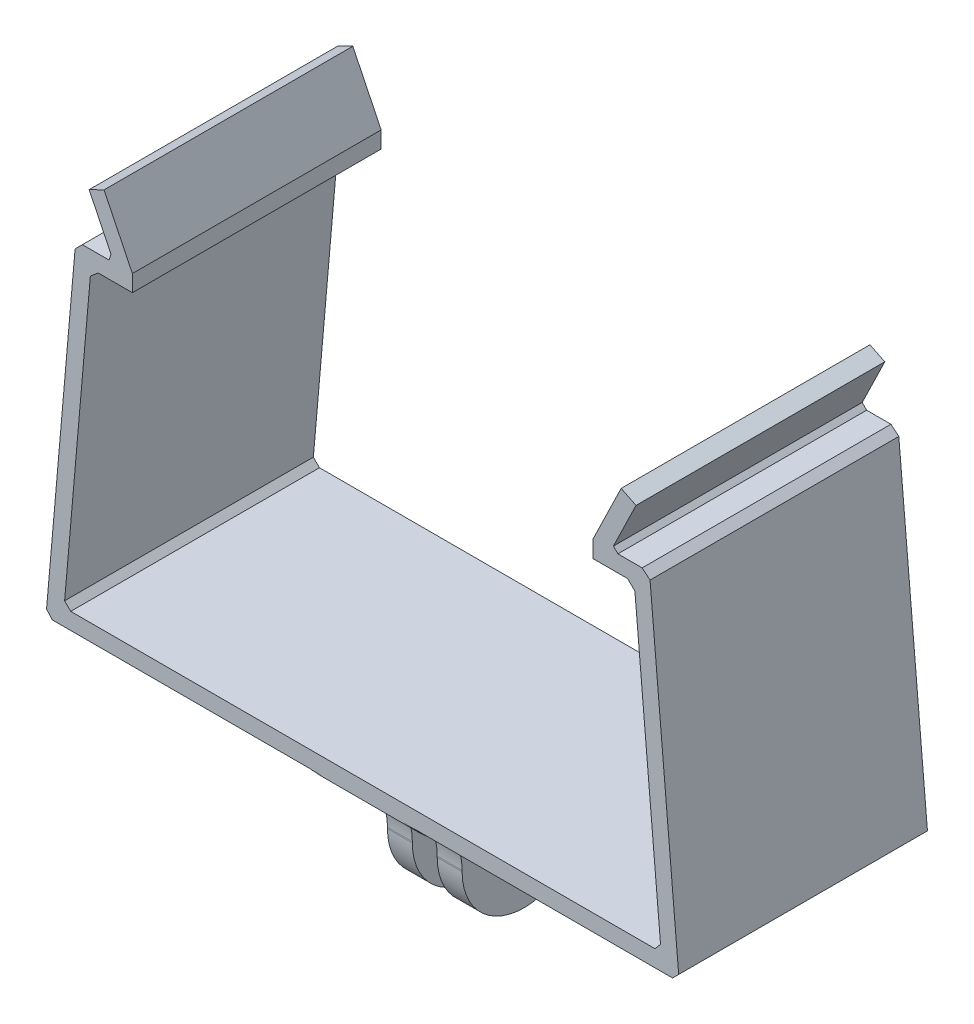
SolidWorks part; units mm, degrees
ref_plane "Front Plane" through (0, 0, 0) normal (0, 0, 1) x (1, 0, 0)
ref_plane "Top Plane" through (0, 0, 0) normal (0, 1, 0) x (1, 0, 0)
ref_plane "Right Plane" through (0, 0, 0) normal (1, 0, 0) x (0, 0, -1)
sketch "Sketch1" plane through (0, 0, 0) normal (0, 0, 1) x (1, 0, 0)
  line L0 (0, 0) -> (0, 24) construction
  line L1 (-34.5956, 39) -> (-29.9866, 39)
  line L2 (-32.7629, 37) -> (-36, 0)
  line L3 (-36, 0) -> (0, 0)
  line L4 (-34.5956, 39) -> (-38.1826, -2)
  line L5 (-38.1826, -2) -> (0, -2)
  line L6 (-32.7629, 37) -> (-27.7629, 37)
  line L7 (-27.7629, 39) -> (-27.7629, 37)
  line L8 (38.1826, -2) -> (0, -2)
  line L9 (36, 0) -> (0, 0)
  line L10 (27.7629, 39) -> (27.7629, 37)
  line L11 (32.7629, 37) -> (27.7629, 37)
  line L12 (34.5956, 39) -> (38.1826, -2)
  line L13 (32.7629, 37) -> (36, 0)
  line L14 (34.5956, 39) -> (29.9866, 39)
  line L15 (-27.7629, 39) -> (-31.1793, 46.0303)
  line L16 (-29.9866, 39) -> (-32.9781, 45.1562)
  line L17 (-31.1793, 46.0303) -> (-32.9781, 45.1562)
  line L18 (-29.5618, 38.1259) -> (-32.9781, 45.1562) construction
  line L19 (-34.5956, 39) -> (-27.7629, 39) construction
  line L20 (31.1793, 46.0303) -> (32.9781, 45.1562)
  line L21 (29.9866, 39) -> (32.9781, 45.1562)
  line L22 (27.7629, 39) -> (31.1793, 46.0303)
  dimension "D1" = 85
  dimension "D2" = 37
  dimension "D3" = 36
  dimension "D4" = 2
  dimension "D5" = 5
  dimension "D6" = 2
extrude "Boss-Extrude1" add sketch "Sketch1" along normal blind 30
sketch "Sketch5" plane through (0, -2, 0) normal (0, -1, 0) x (1, 0, 0)
  line L0 (-15, 0) -> (-15, 30)
  line L3 (-15, 30) -> (15, 30)
  line L4 (-15, 0) -> (15, 0)
  line L5 (0, 0) -> (0, 50) construction
  line L6 (-38.1826, 30) -> (38.1826, 30) construction
  line L7 (15, 0) -> (15, 30)
  dimension "D1" = 30
extrude "Boss-Extrude2" add sketch "Sketch5" along normal blind 1.6
sketch "Sketch9" plane through (0, 0, 0) normal (0, 1, 0) x (1, 0, 0)
  line L1 (-5, -25) -> (-5, -5)
  line L2 (-5, -25) -> (5, -25)
  line L3 (5, -25) -> (5, -5)
  line L4 (-5, -5) -> (5, -5)
  line L5 (-5, -25) -> (5, -5) construction
  line L6 (5, -25) -> (-5, -5) construction
  point P0 (0, -15)
  dimension "D1" = 10
  dimension "D3" = 20
fillet "Fillet13" radius 10 4 edges at (-15, -2.8, 0) (15, -2.8, 0) (15, -2.8, 30) (-15, -2.8, 30)
chamfer "Chamfer5" distance 1.5 angle 45 8 edges at (15, -3.6, 15) (12.0711, -3.6, 27.0711) (12.0711, -3.6, 2.9289) (0, -3.6, 30) (0, -3.6, 0) (-12.0711, -3.6, 27.0711) (-12.0711, -3.6, 2.9289) (-15, -3.6, 15)
chamfer "Chamfer6" distance 0.8 angle 45 4 edges at (-38.1826, -2, 15) (38.1826, -2, 15) (36, 0, 15) (-36, 0, 15)
chamfer "Chamfer7" distance 0.8 angle 45 6 edges at (-32.7629, 37, 15) (32.7629, 37, 15) (34.5956, 39, 15) (-34.5956, 39, 15) (29.9866, 39, 15) (-29.9866, 39, 15)
sketch "Sketch10" plane through (0, -3.6, 0) normal (0, -1, 0) x (1, 0, 0)
  line L1 (-4.5, 7.5) -> (4.5, 7.5)
  line L2 (-4.5, 7.5) -> (-4.5, 22.5)
  line L3 (-4.5, 22.5) -> (4.5, 22.5)
  line L4 (4.5, 7.5) -> (4.5, 22.5)
  line L5 (-4.5, 7.5) -> (4.5, 22.5) construction
  line L6 (-4.5, 22.5) -> (4.5, 7.5) construction
  point P0 (0, 15)
  dimension "D1" = 9
  dimension "D2" = 15
extrude "Boss-Extrude3" add sketch "Sketch10" along normal blind 15
fillet "Fillet14" radius 7.5 4 edges at (0, -3.6, 7.5) (0, -3.6, 22.5) (0, -18.6, 7.5) (0, -18.6, 22.5)
hole_wizard "Ø5.2 (5.2) Diameter Hole1" positions "Sketch11" profile "Sketch12" hole size "Ø5.2" standard "ANSI Metric" end condition through all
sketch "Sketch11" plane through (-4.5, 0, 0) normal (-1, 0, 0) x (0, 0, 1)
  point P0 (15, -11.1)
sketch "Sketch12" plane through (-4.5, -11.1, 15) normal (0, 1, 0) x (0, 0, 1)
  line L0 (0, 0) -> (0, 42.6183)
  line L1 (0, 42.6183) -> (2.6, 42.6183)
  line L2 (2.6, 42.6183) -> (2.6, 0)
  line L5 (2.6, 0) -> (0, 0)
  line L11 (0, -6.35) -> (0, 107.95) construction
  dimension "Thru Hole Dia." = 5.2
  dimension "Thru Hole Depth" = 42.6183
sketch "Sketch13" plane through (0, -3.6, 0) normal (0, -1, 0) x (1, 0, 0)
  line L0 (4.5, 15) -> (-4.5, 15) construction
  line L1 (-1.5, 28.5) -> (1.5, 28.5)
  line L2 (-1.5, 28.5) -> (-1.5, 1.5)
  line L3 (-1.5, 1.5) -> (1.5, 1.5)
  line L4 (1.5, 28.5) -> (1.5, 1.5)
  line L5 (-1.5, 28.5) -> (1.5, 1.5) construction
  line L6 (-1.5, 1.5) -> (1.5, 28.5) construction
  line L7 (-4.5, 1.5) -> (4.5, 1.5) construction
  point P0 (0, 15)
  dimension "D1" = 3
extrude "Cut-Extrude5" cut sketch "Sketch13" along normal blind 15
chamfer "Chamfer8" distance 1.5 angle 45 2 edges at (4.5, -3.6, 15) (-4.5, -3.6, 15)
